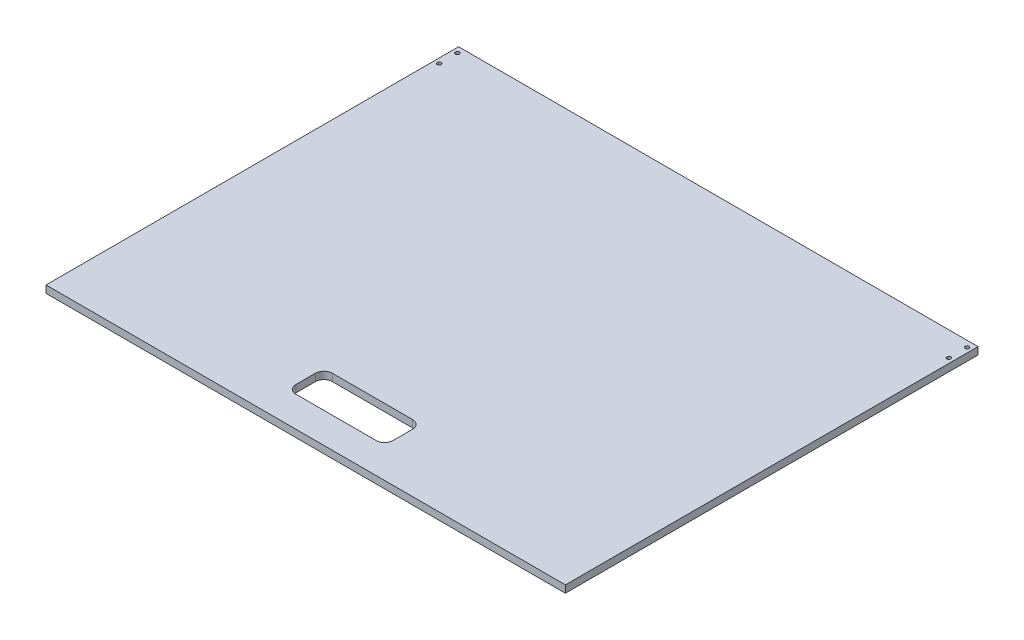
SolidWorks part; units mm, degrees
ref_plane "Front Plane" through (0, 0, 0) normal (0, 0, 1) x (1, 0, 0)
ref_plane "Top Plane" through (0, 0, 0) normal (0, 1, 0) x (1, 0, 0)
ref_plane "Right Plane" through (0, 0, 0) normal (1, 0, 0) x (0, 0, -1)
sketch "Sketch1" plane through (0, 0, 0) normal (0, 1, 0) x (1, 0, 0)
  line L1 (-214, -170) -> (214, -170)
  line L2 (-214, -170) -> (-214, 170)
  line L3 (-214, 170) -> (214, 170)
  line L4 (214, -170) -> (214, 170)
  line L5 (-214, -170) -> (214, 170) construction
  line L6 (-214, 170) -> (214, -170) construction
  point P0 (0, 0)
  dimension "D1" = 428
  dimension "D2" = 340
extrude "Boss-Extrude1" add sketch "Sketch1" along normal blind 6
sketch "Sketch2" plane through (0, 0, 0) normal (0, -1, 0) x (1, 0, 0)
  line L0 (214, -170) -> (-214, -170) construction
  line L1 (214, 170) -> (214, -170) construction
  circle A0 centre (210, -150) radius 1.6
  circle A1 centre (210, -165) radius 1.6
  dimension "D1" = 5
  dimension "D3" = 3.2
  dimension "D2" = 15
  dimension "D4" = 4
extrude "Cut-Extrude1" cut sketch "Sketch2" against normal through all
mirror "Mirror1" about plane through (0, 0, 0) normal (1, 0, 0) of "Cut-Extrude1"
sketch "Sketch3" plane through (0, 6, 0) normal (0, 1, 0) x (1, 0, 0)
  line L0 (-214, -170) -> (214, -170) construction
  line L1 (-33, -145) -> (33, -145)
  line L2 (-40, -138) -> (-40, -122)
  line L3 (-33, -115) -> (33, -115)
  line L4 (40, -138) -> (40, -122)
  line L5 (-40, -145) -> (40, -115) construction
  line L6 (-40, -115) -> (40, -145) construction
  arc A0 (-40, -122) -> (-33, -115) centre (-33, -122) cw
  arc A1 (-33, -145) -> (-40, -138) centre (-33, -138) cw
  arc A2 (33, -145) -> (40, -138) centre (33, -138) ccw
  arc A3 (33, -115) -> (40, -122) centre (33, -122) cw
  point P0 (0, -130)
  dimension "D4" = 7
  dimension "D1" = 25
  dimension "D2" = 80
  dimension "D3" = 30
extrude "Cut-Extrude2" cut sketch "Sketch3" against normal through all
